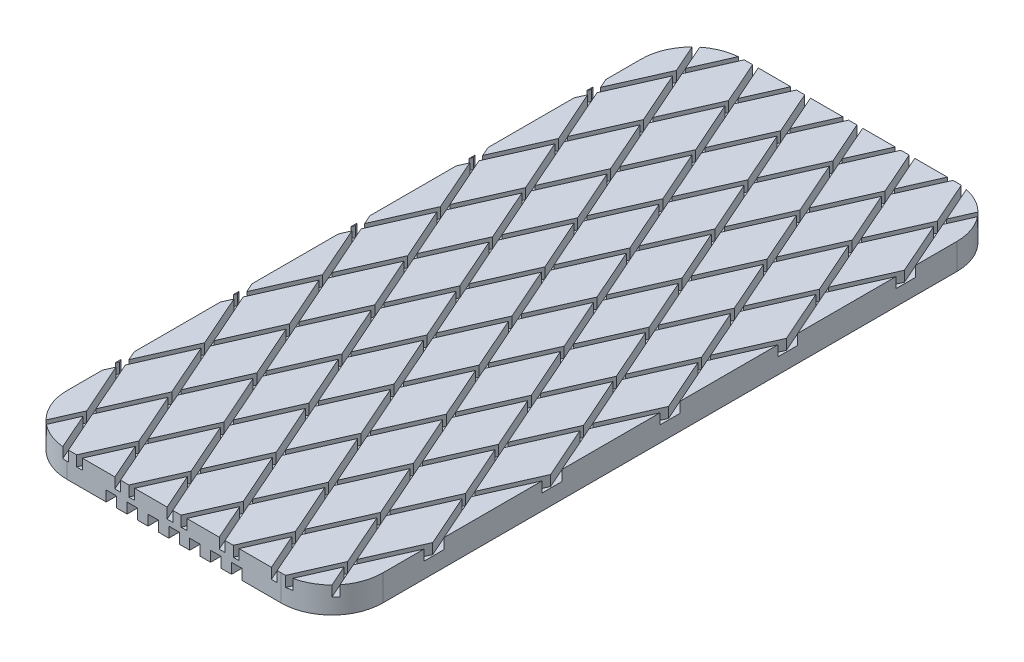
SolidWorks part; units mm, degrees
ref_plane "Front Plane" through (0, 0, 0) normal (0, 0, 1) x (1, 0, 0)
ref_plane "Top Plane" through (0, 0, 0) normal (0, 1, 0) x (1, 0, 0)
ref_plane "Right Plane" through (0, 0, 0) normal (1, 0, 0) x (0, 0, -1)
sketch "Sketch1" plane through (0, 0, 0) normal (0, 1, 0) x (1, 0, 0)
  line L0 (-20.5, 64.75) -> (20.5, 64.75)
  line L1 (-20.5, 65) -> (20.5, 65)
  line L2 (-30.5, 55) -> (-30.5, -55)
  line L3 (-20.5, -65) -> (20.5, -65)
  line L4 (30.5, 55) -> (30.5, -55)
  line L5 (-30.5, 65) -> (30.5, -65) construction
  line L6 (-30.5, -65) -> (30.5, 65) construction
  line L7 (30.25, 55) -> (30.25, -55)
  line L8 (-20.5, -64.75) -> (20.5, -64.75)
  line L9 (-30.25, 55) -> (-30.25, -55)
  arc A0 (-30.5, -55) -> (-20.5, -65) centre (-20.5, -55) ccw
  arc A1 (20.5, -65) -> (30.5, -55) centre (20.5, -55) ccw
  arc A2 (20.5, 65) -> (30.5, 55) centre (20.5, 55) cw
  arc A3 (-20.5, 65) -> (-30.5, 55) centre (-20.5, 55) ccw
  arc A4 (20.5, 64.75) -> (30.25, 55) centre (20.5, 55) cw
  arc A5 (20.5, -64.75) -> (30.25, -55) centre (20.5, -55) ccw
  arc A6 (-30.25, -55) -> (-20.5, -64.75) centre (-20.5, -55) ccw
  arc A7 (-20.5, 64.75) -> (-30.25, 55) centre (-20.5, 55) ccw
  point P0 (0, 0)
  dimension "D3" = 10
  dimension "D1" = 61
  dimension "D2" = 130
  dimension "D4" = 0.25
extrude "Boss-Extrude1" add sketch "Sketch1" along normal blind 5 contours L0 A7 L9 A6 L8 A5 L7 A4 region at (0, 0, 0)
sketch "Sketch2" plane through (0, 5, 0) normal (0, 1, 0) x (1, 0, 0)
  line L0 (27.3943, 61.8943) -> (-27.3943, -61.8943)
  line L1 (27.3943, -61.8943) -> (-27.3943, 61.8943)
  line L2 (-27.3943, -61.8943) -> (-35.5656, -80.3565)
  line L3 (27.3943, -61.8943) -> (37.2077, -84.0665)
  line L4 (27.3943, 61.8943) -> (35.7495, 80.7719)
  line L5 (-27.3943, 61.8943) -> (-35.4548, 80.1061)
  line L6 (37.3943, 61.8943) -> (45.7495, 80.7719)
  line L7 (37.3943, 61.8943) -> (-17.3943, -61.8943)
  line L8 (-17.3943, -61.8943) -> (-25.5656, -80.3565)
  line L9 (37.3943, -61.8943) -> (-17.3943, 61.8943)
  line L10 (-17.3943, 61.8943) -> (-25.4548, 80.1061)
  line L11 (37.3943, -61.8943) -> (47.2077, -84.0665)
  line L12 (47.3943, 61.8943) -> (55.7495, 80.7719)
  line L13 (47.3943, 61.8943) -> (-7.3943, -61.8943)
  line L14 (-7.3943, -61.8943) -> (-15.5656, -80.3565)
  line L15 (47.3943, -61.8943) -> (-7.3943, 61.8943)
  line L16 (-7.3943, 61.8943) -> (-15.4548, 80.1061)
  line L17 (47.3943, -61.8943) -> (57.2077, -84.0665)
  line L18 (57.3943, 61.8943) -> (65.7495, 80.7719)
  line L19 (57.3943, 61.8943) -> (2.6057, -61.8943)
  line L20 (2.6057, -61.8943) -> (-5.5656, -80.3565)
  line L21 (57.3943, -61.8943) -> (2.6057, 61.8943)
  line L22 (2.6057, 61.8943) -> (-5.4548, 80.1061)
  line L23 (57.3943, -61.8943) -> (67.2077, -84.0665)
  line L24 (67.3943, 61.8943) -> (75.7495, 80.7719)
  line L25 (67.3943, 61.8943) -> (12.6057, -61.8943)
  line L26 (12.6057, -61.8943) -> (4.4344, -80.3565)
  line L27 (67.3943, -61.8943) -> (12.6057, 61.8943)
  line L28 (12.6057, 61.8943) -> (4.5452, 80.1061)
  line L29 (67.3943, -61.8943) -> (77.2077, -84.0665)
  line L30 (77.3943, 61.8943) -> (85.7495, 80.7719)
  line L31 (77.3943, 61.8943) -> (22.6057, -61.8943)
  line L32 (22.6057, -61.8943) -> (14.4344, -80.3565)
  line L33 (77.3943, -61.8943) -> (22.6057, 61.8943)
  line L34 (22.6057, 61.8943) -> (14.5452, 80.1061)
  line L35 (77.3943, -61.8943) -> (87.2077, -84.0665)
  line L36 (17.3943, 61.8943) -> (25.7495, 80.7719)
  line L37 (17.3943, 61.8943) -> (-37.3943, -61.8943)
  line L38 (-37.3943, -61.8943) -> (-45.5656, -80.3565)
  line L39 (17.3943, -61.8943) -> (-37.3943, 61.8943)
  line L40 (-37.3943, 61.8943) -> (-45.4548, 80.1061)
  line L41 (17.3943, -61.8943) -> (27.2077, -84.0665)
  line L42 (7.3943, 61.8943) -> (15.7495, 80.7719)
  line L43 (7.3943, 61.8943) -> (-47.3943, -61.8943)
  line L44 (-47.3943, -61.8943) -> (-55.5656, -80.3565)
  line L45 (7.3943, -61.8943) -> (-47.3943, 61.8943)
  line L46 (-47.3943, 61.8943) -> (-55.4548, 80.1061)
  line L47 (7.3943, -61.8943) -> (17.2077, -84.0665)
  line L48 (-2.6057, 61.8943) -> (5.7495, 80.7719)
  line L49 (-2.6057, 61.8943) -> (-57.3943, -61.8943)
  line L50 (-57.3943, -61.8943) -> (-65.5656, -80.3565)
  line L51 (-2.6057, -61.8943) -> (-57.3943, 61.8943)
  line L52 (-57.3943, 61.8943) -> (-65.4548, 80.1061)
  line L53 (-2.6057, -61.8943) -> (7.2077, -84.0665)
  line L54 (-12.6057, 61.8943) -> (-4.2505, 80.7719)
  line L55 (-12.6057, 61.8943) -> (-67.3943, -61.8943)
  line L56 (-67.3943, -61.8943) -> (-75.5656, -80.3565)
  line L57 (-12.6057, -61.8943) -> (-67.3943, 61.8943)
  line L58 (-67.3943, 61.8943) -> (-75.4548, 80.1061)
  line L59 (-12.6057, -61.8943) -> (-2.7923, -84.0665)
  line L60 (-22.6057, 61.8943) -> (-14.2505, 80.7719)
  line L61 (-22.6057, 61.8943) -> (-77.3943, -61.8943)
  line L62 (-77.3943, -61.8943) -> (-85.5656, -80.3565)
  line L63 (-22.6057, -61.8943) -> (-77.3943, 61.8943)
  line L64 (-77.3943, 61.8943) -> (-85.4548, 80.1061)
  line L65 (-22.6057, -61.8943) -> (-12.7923, -84.0665)
  arc A0 (30.25, 55) -> (20.5, 64.75) centre (20.5, 55) ccw construction
  arc A1 (-30.25, -55) -> (-20.5, -64.75) centre (-20.5, -55) ccw construction
  arc A2 (20.5, -64.75) -> (30.25, -55) centre (20.5, -55) ccw construction
  arc A3 (-20.5, 64.75) -> (-30.25, 55) centre (-20.5, 55) ccw construction
  dimension "D1" = 6
  dimension "D2" = 6
extrude "Cut-Extrude-Thin2" cut sketch "Sketch2" against normal blind 2 thin thin type one direction wall 1
sketch "Sketch3" plane through (0, 0, 0) normal (0, -1, 0) x (-1, 0, 0)
  line L0 (0, -64.75) -> (0, 64.75)
  line L1 (20.5, -64.75) -> (-20.5, -64.75) construction
  line L2 (20.5, 64.75) -> (-20.5, 64.75) construction
  line L3 (4, -64.75) -> (4, 64.75)
  line L4 (8, -64.75) -> (8, 64.75)
  line L5 (12, -64.75) -> (12, 64.75)
  line L6 (-4, -64.75) -> (-4, 64.75)
  line L7 (-8, -64.75) -> (-8, 64.75)
  line L8 (-12, -64.75) -> (-12, 64.75)
  dimension "D1" = 4
  dimension "D2" = 4
extrude "Cut-Extrude-Thin3" cut sketch "Sketch3" against normal blind 2 thin thin type mid plane wall 2
